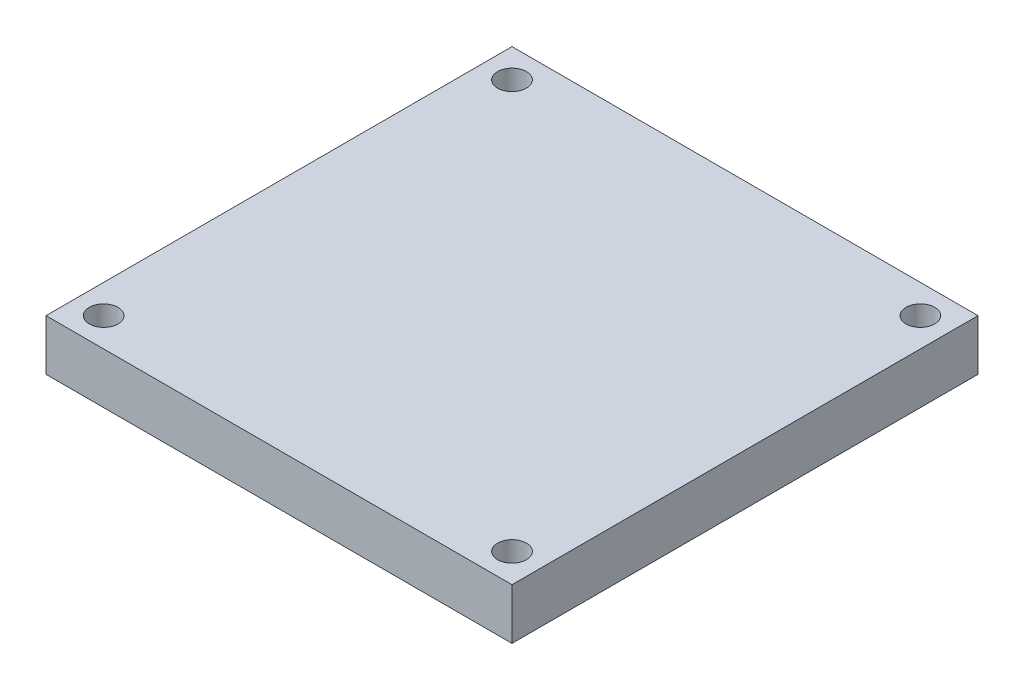
SolidWorks part; units mm, degrees
ref_plane "Front Plane" through (0, 0, 0) normal (0, 0, 1) x (1, 0, 0)
ref_plane "Top Plane" through (0, 0, 0) normal (0, 1, 0) x (1, 0, 0)
ref_plane "Right Plane" through (0, 0, 0) normal (1, 0, 0) x (0, 0, -1)
sketch "Sketch1" plane through (0, 0, 0) normal (0, 1, 0) x (1, 0, 0)
  line L1 (-27.495, -27.495) -> (27.495, -27.495)
  line L2 (-27.495, -27.495) -> (-27.495, 27.495)
  line L3 (-27.495, 27.495) -> (27.495, 27.495)
  line L4 (27.495, -27.495) -> (27.495, 27.495)
  line L5 (-27.495, -27.495) -> (27.495, 27.495) construction
  line L6 (-27.495, 27.495) -> (27.495, -27.495) construction
  point P0 (0, 0)
  dimension "D1" = 54.99
extrude "Boss-Extrude1" add sketch "Sketch1" along normal blind 6
sketch "Sketch5" plane through (0, 6, 0) normal (0, 1, 0) x (1, 0, 0)
  line L0 (-27.495, 27.495) -> (-27.495, -27.495) construction
  line L1 (27.495, -27.495) -> (27.495, 27.495) construction
  line L2 (27.495, 27.495) -> (-27.495, 27.495) construction
  line L3 (-27.495, -27.495) -> (27.495, -27.495) construction
  point P0 (-24.095, 24.095)
  point P1 (24.095, 24.095)
  point P2 (24.095, -24.095)
  point P3 (-24.095, -24.095)
  dimension "D1" = 3.4
  dimension "D2" = 3.4
  dimension "D3" = 3.4
  dimension "D4" = 3.4
  dimension "D5" = 3.4
  dimension "D6" = 3.4
  dimension "D7" = 3.4
  dimension "D8" = 3.4
hole_wizard "M3 Clearance Hole2" positions "Sketch6" profile "Sketch7" hole size "M3" standard "ANSI Metric" end condition through all
sketch "Sketch6" plane through (0, 6, 0) normal (0, 1, 0) x (1, 0, 0)
  point P0 (-24.095, 24.095)
  point P3 (24.095, 24.095)
  point P6 (24.095, -24.095)
  point P9 (-24.095, -24.095)
sketch "Sketch7" plane through (-24.095, 6, -24.095) normal (1, 0, 0) x (0, 0, 1)
  line L0 (0, 0) -> (0, 6)
  line L1 (0, 6) -> (1.7, 6)
  line L2 (1.7, 6) -> (1.7, 0)
  line L5 (1.7, 0) -> (0, 0)
  line L11 (0, -6.35) -> (0, 107.95) construction
  dimension "Thru Hole Dia." = 3.4
  dimension "Thru Hole Depth" = 6
